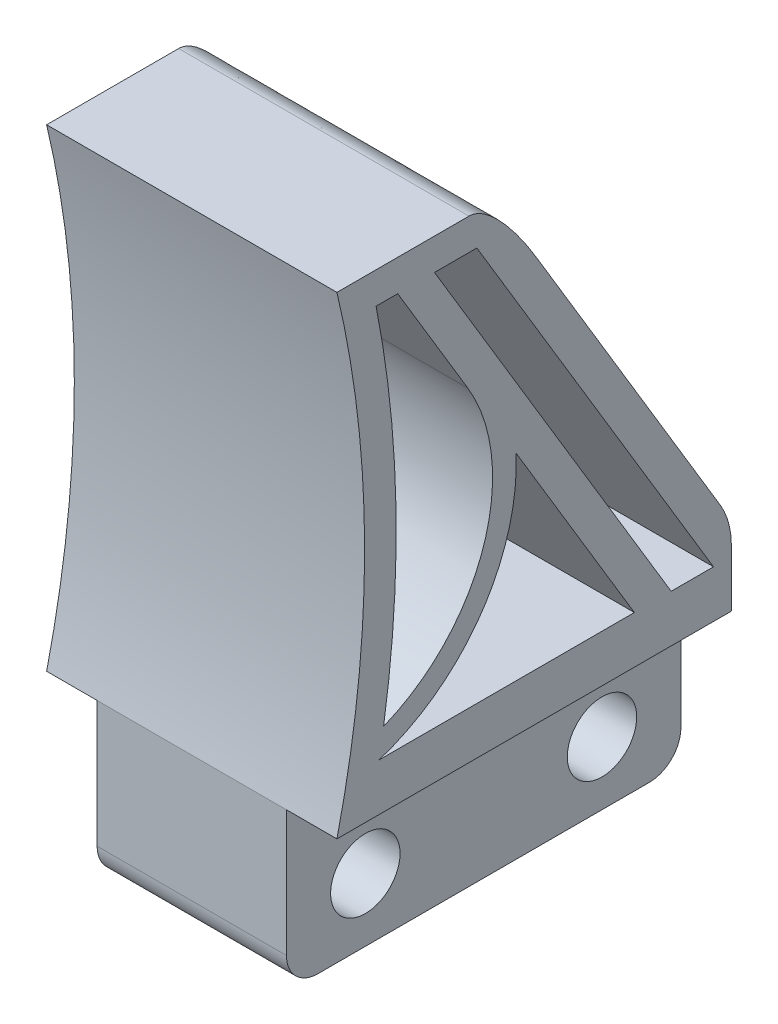
SolidWorks part; units mm, degrees
ref_plane "Front Plane" through (0, 0, 0) normal (0, 0, 1) x (1, 0, 0)
ref_plane "Top Plane" through (0, 0, 0) normal (0, 1, 0) x (1, 0, 0)
ref_plane "Right Plane" through (0, 0, 0) normal (1, 0, 0) x (0, 0, -1)
sketch "Sketch1" plane through (0, 0, 0) normal (1, 0, 0) x (0, 0, -1)
  line L0 (0, 0) -> (25, 0)
  line L4 (10, 30) -> (0, 30)
  line L5 (25, 0) -> (25, 5)
  line L6 (25, 5) -> (10, 30)
  line L7 (8.8676, 28) -> (23.8676, 3)
  line L9 (21.1854, 3) -> (6.1854, 28)
  line L11 (8.8676, 28) -> (6.1854, 28)
  line L12 (21.1854, 3) -> (23.8676, 3)
  line L13 (3.853, 28) -> (18.853, 3)
  line L14 (18.853, 3) -> (2.6711, 3)
  line L15 (3.853, 28) -> (2.4812, 28)
  arc A0 (0, 30) -> (0, 0) centre (-63.2456, 15) cw
  arc A2 (2.4812, 28) -> (2.6711, 3) centre (-63.2456, 15) cw
  arc A3 (8.2952, 20.5963) -> (2.9576, 4.6973) centre (-1.1579, 14.9244) cw
  arc A4 (11.353, 15.5) -> (2.6711, 3) centre (-1.1579, 14.9244) cw
  point P26 (11.353, 15.5)
  dimension "D4" = 5
  dimension "D5" = 65
  dimension "D10" = 2
  dimension "D11" = 2
  dimension "D12" = 1.5
  dimension "D1" = 25
  dimension "D2" = 30
  dimension "D3" = 10
  dimension "D6" = 2.3
  dimension "D7" = 2
  dimension "D8" = 3
  dimension "D9" = 2
extrude "Boss-Extrude1" add sketch "Sketch1" along normal blind 18.4 contours L4 A0 L0 L5 L6 A2 L15 L13 L14 L12 L9 L11 L7 | A4 L13 A3 A2 region at (0, 15, -2.145) region at (0, 17.9472, -9.6558)
fillet "Fillet1" radius 7 1 edges at (9.2, 30, -10) second distance 5 first distance on face at (9.2, 17.5, -17.5)
fillet "Fillet2" radius 5 1 edges at (9.2, 5, -25)
sketch "Sketch2" plane through (0, 0, 0) normal (0, -1, 0) x (-1, 0, 0)
  line L6 (-18.4, 0) -> (0, 0) construction
  line L7 (-3.2, 0) -> (-15.2, 0)
  line L8 (-3.2, 0) -> (-3.2, 25)
  line L9 (-3.2, 25) -> (-15.2, 25)
  line L10 (-15.2, 0) -> (-15.2, 25)
  line L11 (-18.4, 25) -> (0, 25) construction
  point P8 (-9.2, 25)
  point P9 (-9.2, 25)
  dimension "D1" = 12
extrude "Boss-Extrude2" add sketch "Sketch2" along normal blind 10
sketch "Sketch3" plane through (15.2, 0, 0) normal (1, 0, 0) x (0, 0, -1)
  line L0 (25, -10) -> (0, -10) construction
  line L1 (5, -6) -> (20, -6) construction
  circle A0 centre (5, -6) radius 2.2
  circle A1 centre (20, -6) radius 2.2
  point P4 (12.5, -10)
  point P7 (12.5, -6)
  dimension "D1" = 15
  dimension "D2" = 4
  dimension "D3" = 4.4
extrude "Cut-Extrude1" cut sketch "Sketch3" against normal through all
fillet "Fillet3" radius 2 2 edges at (9.2, -10, 0) (9.2, -10, -25)
